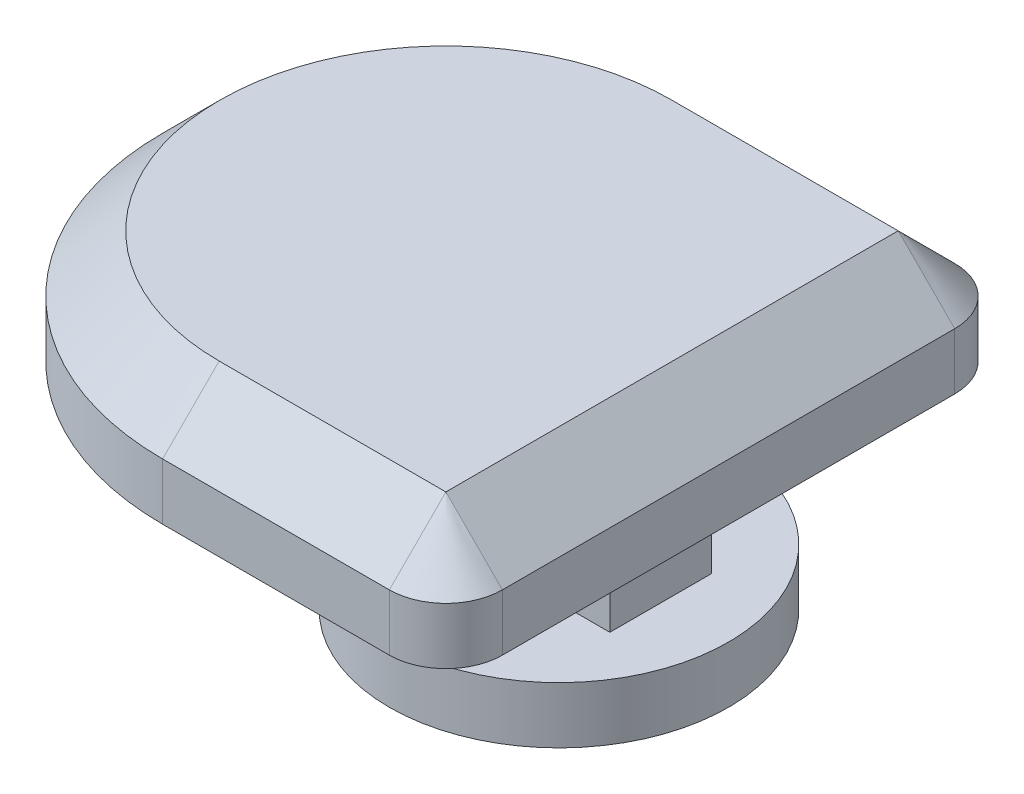
SolidWorks part; units mm, degrees
ref_plane "前视基准面" through (0, 0, 0) normal (0, 0, 1) x (1, 0, 0)
ref_plane "上视基准面" through (0, 0, 0) normal (0, 1, 0) x (1, 0, 0)
ref_plane "右视基准面" through (0, 0, 0) normal (1, 0, 0) x (0, 0, -1)
sketch "草图1" plane through (0, 0, 0) normal (0, 1, 0) x (1, 0, 0)
  circle A0 centre (0, 0) radius 3
extrude "凸台-拉伸1" add sketch "草图1" along normal blind 1
sketch "草图2" plane through (0, 1, 0) normal (0, 1, 0) x (1, 0, 0)
  line L1 (-1.8, 0.9) -> (1.8, 0.9)
  line L2 (-1.8, 0.9) -> (-1.8, -0.9)
  line L3 (-1.8, -0.9) -> (1.8, -0.9)
  line L4 (1.8, 0.9) -> (1.8, -0.9)
  line L5 (-1.8, 0.9) -> (1.8, -0.9) construction
  line L6 (-1.8, -0.9) -> (1.8, 0.9) construction
  point P0 (0, 0)
extrude "凸台-拉伸2" add sketch "草图2" along normal blind 1.8
sketch "草图3" plane through (0, 2.8, 0) normal (0, 1, 0) x (1, 0, 0)
  line L0 (3, 5) -> (3, -5) construction
  line L2 (2, 5) -> (-2.01, 5)
  line L3 (3, 4) -> (3, -4)
  line L4 (2, -5) -> (-2.01, -5)
  line L5 (-7, 0.01) -> (-7, -0.01)
  circle A0 centre (0, 0) radius 3 construction
  arc A1 (-7, -0.01) -> (-2.01, -5) centre (-2.01, -0.01) ccw
  arc A2 (-2.01, 5) -> (-7, 0.01) centre (-2.01, 0.01) ccw
  arc A3 (3, -4) -> (2, -5) centre (2, -4) cw
  arc A4 (3, 4) -> (2, 5) centre (2, 4) ccw
  point P6 (3, 0)
  dimension "D1" = 4.99
  dimension "D2" = 1
extrude "凸台-拉伸3" add sketch "草图3" along normal blind 2
chamfer "倒角1" distance 1 angle 45 8 edges at (2.7071, 4.8, -4.7071) (-0.005, 4.8, -5) (3, 4.8, 0) (-5.5385, 4.8, -3.5385) (2.7071, 4.8, 4.7071) (-7, 4.8, 0) (-0.005, 4.8, 5) (-5.5385, 4.8, 3.5385)
